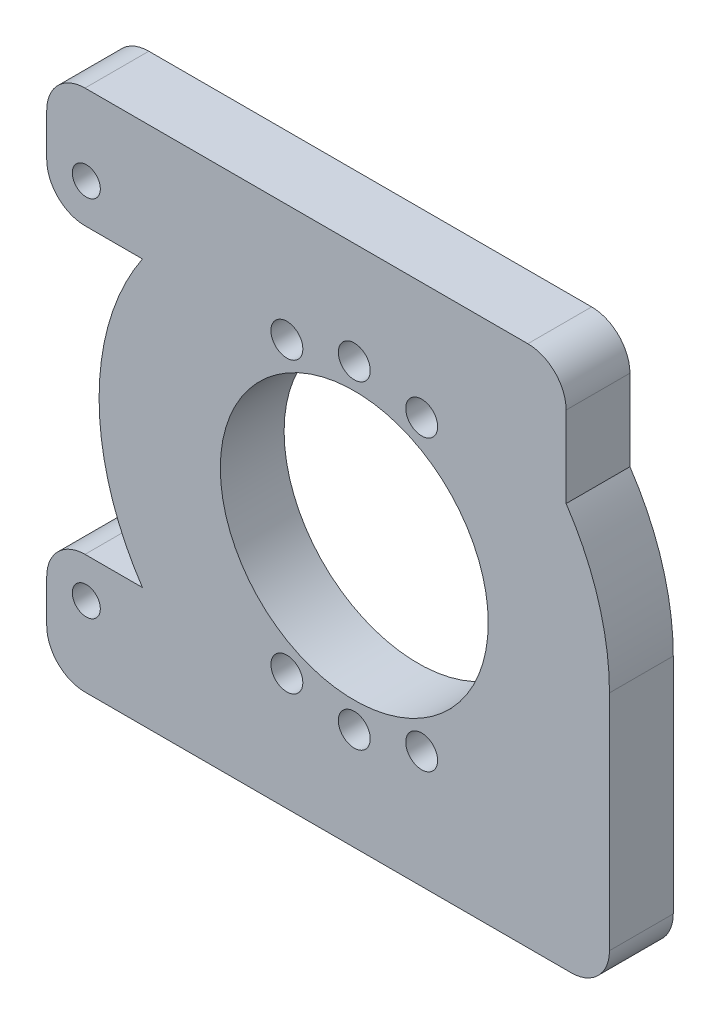
SolidWorks part; units mm, degrees
ref_plane "Front Plane" through (0, 0, 0) normal (0, 0, 1) x (1, 0, 0)
ref_plane "Top Plane" through (0, 0, 0) normal (0, 1, 0) x (1, 0, 0)
ref_plane "Right Plane" through (0, 0, 0) normal (1, 0, 0) x (0, 0, -1)
sketch "Sketch1" plane through (0, 0, 0) normal (0, 0, 1) x (1, 0, 0)
  line L0 (0, 0) -> (0, 27.5) construction
  line L1 (0, 0) -> (11.622, 24.9235) construction
  line L2 (0, 0) -> (-11.622, 24.9235) construction
  line L3 (0, 0) -> (11.622, -24.9235) construction
  line L4 (0, 0) -> (0, -27.5) construction
  line L5 (0, 0) -> (-11.622, -24.9235) construction
  line L6 (0, 0) -> (-60.8338, 0) construction
  line L7 (-40, 0) -> (-40, 22.3) construction
  line L8 (-40, 0) -> (-40, -22.3) construction
  line L9 (-40, -22.3) -> (-33.2071, -22.3) construction
  line L10 (-40, 22.3) -> (-33.2071, 22.3) construction
  line L11 (-33.2071, 22.3) -> (-42.2071, 22.3)
  line L12 (-48.2071, 28.3) -> (-48.2071, 30)
  line L13 (0, 41) -> (-42.2071, 41)
  line L14 (-33.2071, -22.3) -> (-42.2071, -22.3)
  line L15 (-48.2071, -28.3) -> (-48.2071, -30)
  line L17 (-48.2071, 30) -> (-48.2071, 35)
  line L18 (33.2071, 22.3) -> (33.2071, 35)
  line L19 (-13.0397, 22.3) -> (13.0397, 22.3) construction
  line L20 (-48.2071, -30) -> (-48.2071, -34.7)
  line L21 (27.2071, 41) -> (0, 41)
  line L22 (-42.2071, -41) -> (34, -41)
  line L23 (40, 0) -> (40, -35)
  line L24 (-48.2071, -34.7) -> (-48.2071, -35)
  line L25 (0, 41) -> (0, 47.633) construction
  line L26 (19.1186, 41) -> (19.6401, 42.1183) construction
  line L27 (19.1186, -41) -> (24.2233, -51.9471) construction
  line L28 (0, -41) -> (0, -53.438) construction
  line L29 (-19.1186, -41) -> (-24.2529, -52.0105) construction
  circle A0 centre (0, 0) radius 21
  arc A1 (-33.2071, 22.3) -> (-33.2071, -22.3) centre (0, 0) ccw
  circle A2 centre (0, 25) radius 2.5
  circle A3 centre (0, 0) radius 25 construction
  circle A4 centre (10.5655, 22.6577) radius 2.5
  circle A5 centre (-10.5655, 22.6577) radius 2.5
  circle A6 centre (-10.5655, -22.6577) radius 2.5
  circle A7 centre (0, -25) radius 2.5
  circle A8 centre (10.5655, -22.6577) radius 2.5
  circle A9 centre (-42.0071, 28.5) radius 2.2
  circle A10 centre (-42.0071, -28.5) radius 2.2
  arc A11 (-42.2071, -22.3) -> (-48.2071, -28.3) centre (-42.2071, -28.3) ccw
  arc A12 (-42.2071, 22.3) -> (-48.2071, 28.3) centre (-42.2071, 28.3) cw
  arc A13 (-42.2071, -41) -> (-48.2071, -35) centre (-42.2071, -35) cw
  arc A14 (40, -35) -> (34, -41) centre (34, -35) cw
  arc A15 (27.2071, 41) -> (33.2071, 35) centre (27.2071, 35) cw
  arc A16 (-42.2071, 41) -> (-48.2071, 35) centre (-42.2071, 35) ccw
  arc A17 (40, 0) -> (33.2071, 22.3) centre (0, 0) ccw
  point P35 (-42.0071, 28.5)
  point P38 (-42.0071, -28.5)
  point P48 (33.2071, 22.3)
  point P49 (0, 41)
  point P50 (0, 21)
  point P62 (33.2071, 41)
  dimension "D1" = 5
  dimension "D2" = 42
  dimension "D3" = 80
  dimension "D4" = 25
  dimension "D5" = 25
  dimension "D6" = 5
  dimension "D9" = 5
  dimension "D10" = 5
  dimension "D11" = 5
  dimension "D12" = 5
  dimension "D21" = 4.4
  dimension "D24" = 4.4
  dimension "D25" = 6
  dimension "D28" = 6
  dimension "D7" = 25
  dimension "D8" = 25
  dimension "D13" = 22.3
  dimension "D14" = 22.3
  dimension "D16" = 18.7
  dimension "D17" = 15
  dimension "D18" = 15
  dimension "D19" = 6.2
  dimension "D20" = 6.2
  dimension "D22" = 6.2
  dimension "D23" = 6.2
  dimension "D27" = 20
extrude "Boss-Extrude3" add sketch "Sketch1" along normal blind 10
